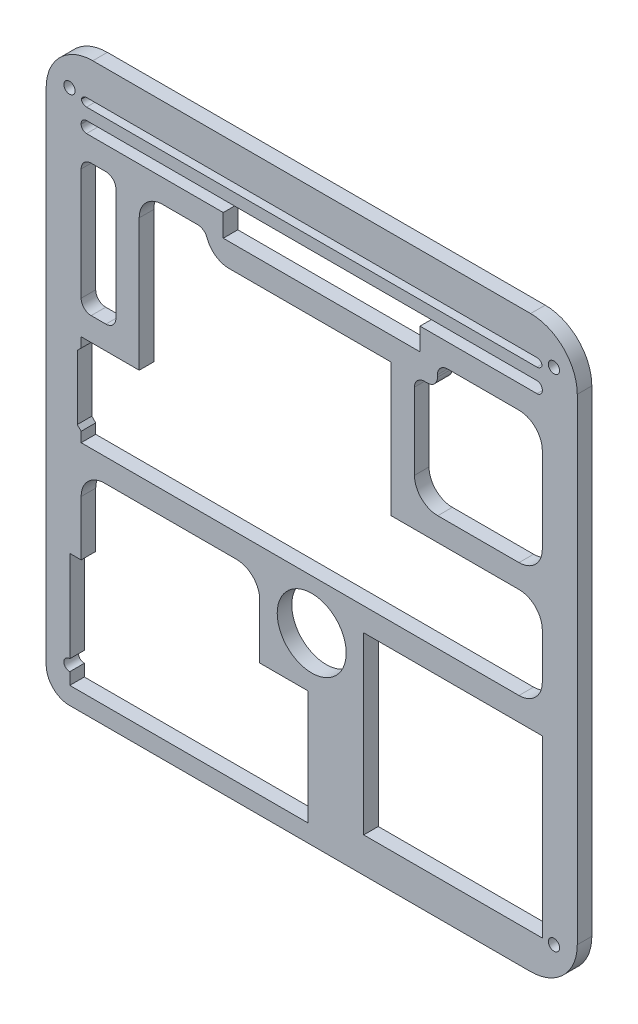
SolidWorks part; units mm, degrees
ref_plane "Front Plane" through (0, 0, 0) normal (0, 0, 1) x (1, 0, 0)
ref_plane "Top Plane" through (0, 0, 0) normal (0, 1, 0) x (1, 0, 0)
ref_plane "Right Plane" through (0, 0, 0) normal (1, 0, 0) x (0, 0, -1)
sketch "Sketch1" plane through (0, 0, 0) normal (0, 0, 1) x (1, 0, 0)
  line L0 (63.9883, 52.5442) -> (63.9883, 48.7342) construction
  line L1 (6.1648, -9.556) -> (64.0322, -9.556)
  line L2 (6.1648, -9.556) -> (6.1648, 52.5442)
  line L3 (6.1648, 52.5442) -> (64.0322, 52.5442)
  line L4 (64.0322, -9.556) -> (64.0322, 52.5442)
  line L5 (60.2222, 48.7342) -> (9.9748, 48.7342)
  line L6 (60.2222, 48.7342) -> (60.2222, -5.746)
  line L7 (60.2222, -5.746) -> (9.9748, -5.746)
  line L8 (9.9748, 48.7342) -> (9.9748, -5.746)
  line L9 (63.9883, 50.6392) -> (18.0707, 50.6392) construction
  line L10 (9.9748, 39.3805) -> (6.1648, 39.3805) construction
  line L11 (8.0698, 39.3805) -> (8.0698, 23.9527) construction
  line L12 (13.5248, -5.746) -> (13.5248, -9.556) construction
  line L13 (13.5248, -7.651) -> (21.1598, -7.651) construction
  line L14 (64.0322, 38.1916) -> (60.2222, 38.1916) construction
  line L15 (62.1272, 38.1916) -> (62.1272, 22.3321) construction
  line L16 (48.6748, 50.6392) -> (23.5288, 50.6392) construction
  line L17 (62.1272, 27.1202) -> (62.1272, 39.363) construction
  line L18 (8.0698, 15.868) -> (8.0698, 3.6252) construction
  line L19 (35.2238, -7.651) -> (34.6952, -7.651) construction
  dimension "D1" = 3.81
  dimension "D2" = 3.81
extrude "Boss-Extrude1" add sketch "Sketch1" along normal blind 1.5875
sketch "Sketch2" plane through (0, 0, 0) normal (0, 0, -1) x (-1, 0, 0)
  line L0 (-60.2222, -5.746) -> (-60.2222, 48.7342) construction
  line L1 (-60.2222, 15.868) -> (-9.9748, 15.868)
  line L2 (-60.2222, 15.868) -> (-60.2222, 13.328)
  line L3 (-60.2222, 13.328) -> (-9.9748, 13.328)
  line L4 (-9.9748, 15.868) -> (-9.9748, 13.328)
  line L5 (-9.9748, 48.7342) -> (-9.9748, -5.746) construction
  line L6 (-13.0532, 15.868) -> (-50.7532, 15.868) construction
  line L8 (-46.8968, 42.9049) -> (-46.8968, 45.3306) construction
  line L9 (-25.4592, 42.9049) -> (-46.8968, 42.9049) construction
  line L10 (-25.4592, 42.9049) -> (-25.4592, 45.3306) construction
  line L11 (-60.2222, 45.3306) -> (-46.8968, 45.3306)
  line L12 (-60.2222, 45.3306) -> (-60.2222, 42.7906)
  line L13 (-60.2222, 42.7906) -> (-48.8018, 42.7906)
  line L14 (-9.9748, 45.3306) -> (-9.9748, 42.7906)
  line L15 (-60.2222, 47.8325) -> (-9.9748, 47.8325)
  line L16 (-60.2222, 47.8325) -> (-60.2222, 46.5625)
  line L17 (-60.2222, 46.5625) -> (-9.9748, 46.5625)
  line L18 (-9.9748, 47.8325) -> (-9.9748, 46.5625)
  line L20 (-55.2788, 45.3306) -> (-16.9248, 45.3306) construction
  line L21 (-55.2788, 46.5625) -> (-16.9248, 46.5625) construction
  line L22 (-46.8968, 42.9049) -> (-46.8968, 45.3306)
  line L23 (-25.4592, 42.9049) -> (-46.8968, 42.9049)
  line L24 (-25.4592, 42.9049) -> (-25.4592, 45.3306)
  line L25 (-48.8018, 42.7906) -> (-48.8018, 40.3649)
  line L26 (-48.8018, 40.3649) -> (-23.5542, 40.3649)
  line L27 (-23.5542, 40.3649) -> (-23.5542, 42.7906)
  line L28 (-23.5542, 42.7906) -> (-9.9748, 42.7906)
  line L29 (-25.4592, 45.3306) -> (-9.9748, 45.3306)
  dimension "D1" = 2.54
  dimension "D2" = 1.905
  dimension "D3" = 2.54
  dimension "D4" = 1.905
  dimension "D5" = 1.27
extrude "Boss-Extrude2" add sketch "Sketch2" against normal up to surface (1.5875 mm away) up to face at (35.0985, 21.4941, 1.5875)
sketch "Sketch3" plane through (0, 0, 0) normal (0, 0, -1) x (-1, 0, 0)
  line L0 (-50.7532, 25.868) -> (-43.7532, 25.868) construction
  line L1 (-50.7532, 25.868) -> (-43.7532, 25.868)
  line L2 (-50.7532, 25.868) -> (-60.2222, 25.868)
  line L3 (-60.2222, 15.868) -> (-60.2222, 42.7906) construction
  line L4 (-60.2222, 25.868) -> (-60.2222, 28.408)
  line L5 (-60.2222, 28.408) -> (-46.2932, 28.408)
  line L6 (-43.7532, 28.408) -> (-43.7532, 25.868)
  line L7 (-43.7532, 28.408) -> (-43.7532, 40.3649)
  line L8 (-48.8018, 40.3649) -> (-23.5542, 40.3649) construction
  line L9 (-43.7532, 40.3649) -> (-46.2932, 40.3649)
  line L10 (-46.2932, 40.3649) -> (-46.2932, 28.408)
  line L11 (-16.3032, 25.868) -> (-13.0532, 25.868) construction
  line L12 (-16.3032, 25.868) -> (-13.0532, 25.868)
  line L13 (-13.0532, 25.868) -> (-9.9748, 25.868)
  line L14 (-9.9748, 42.7906) -> (-9.9748, 15.868) construction
  line L15 (-9.9748, 25.868) -> (-9.9748, 28.408)
  line L16 (-9.9748, 28.408) -> (-13.7632, 28.408)
  line L17 (-13.7632, 28.408) -> (-13.7632, 42.7906)
  line L18 (-23.5542, 42.7906) -> (-9.9748, 42.7906) construction
  line L19 (-13.7632, 42.7906) -> (-16.3032, 42.7906)
  line L20 (-16.3032, 42.7906) -> (-16.3032, 25.868)
  line L21 (-16.3032, 25.868) -> (-16.2412, 25.8471)
  line M22 (-60.2222, 15.868) -> (-60.2222, 42.7906)
  line M25 (-48.8018, 40.3649) -> (-23.5542, 40.3649)
  line M27 (-23.5542, 42.7906) -> (-9.9748, 42.7906)
  line M28 (-9.9748, 42.7906) -> (-9.9748, 15.868)
  dimension "D1" = 2.54
  dimension "D2" = 2.54
  dimension "D3" = 2.54
  dimension "D4" = 2.54
extrude "Boss-Extrude3" add sketch "Sketch3" against normal up to surface (1.5875 mm away) contours L10 L5 L2 L1 L6 L7 M25 M22 | L20 L12 L13 L16 L17 M27 M28 region at (55.4877, 26.0875, 0) region at (14.4544, 33.0139, 0) up to face at (35.0985, 48.2834, 1.5875)
sketch "Sketch4" plane through (0, 0, 0) normal (0, 0, -1) x (-1, 0, 0)
  line L0 (-60.2222, 13.328) -> (-9.9748, 13.328) construction
  line L1 (-40.7627, 13.328) -> (-29.4343, 13.328)
  line L2 (-40.7627, 13.328) -> (-40.7627, -5.746)
  line L3 (-40.7627, -5.746) -> (-29.4343, -5.746)
  line L4 (-29.4343, 13.328) -> (-29.4343, -5.746)
  line L5 (-9.9748, -5.746) -> (-60.2222, -5.746) construction
  line L6 (-38.8577, 10.4578) -> (-40.7627, 10.4578) construction
  line L7 (-31.3393, 10.4578) -> (-29.4343, 10.4578) construction
  circle A0 centre (-35.0985, 10.4578) radius 3.7592 construction
  dimension "D1" = 1.905
extrude "Boss-Extrude4" add sketch "Sketch4" against normal up to surface (1.5875 mm away) up to face at (11.869, 35.5993, 1.5875)
sketch "Sketch5" plane through (0, 0, 0) normal (0, 0, -1) x (-1, 0, 0)
  line L0 (-8.7364, 4.8077) -> (-34.6952, 4.8077) construction
  line L3 (-34.6952, -7.651) -> (-34.6952, 4.8077) construction
  line L4 (-8.7364, -7.651) -> (-34.6952, -7.651) construction
  line L5 (-8.7364, -7.651) -> (-8.7364, 4.8077) construction
  line L6 (-8.7364, 4.8077) -> (-34.6952, 4.8077)
  line L7 (-34.6952, -7.651) -> (-34.6952, 4.8077)
  line L8 (-8.7364, -7.651) -> (-34.6952, -7.651)
  line L9 (-8.7364, -7.651) -> (-8.7364, 4.8077)
  circle A0 centre (-35.0985, 10.4578) radius 3.7592 construction
  circle A1 centre (-35.0985, 10.4578) radius 3.7592
extrude "Cut-Extrude1" cut sketch "Sketch5" against normal up to surface (1.5875 mm away) up to face at (50.4924, 3.791, 1.5875)
fillet "Fillet1" radius 5.08 3 edges at (64.0322, -9.556, 0.7937) (6.1648, 52.5442, 0.7937) (64.0322, 52.5442, 0.7937)
fillet "Fillet2" radius 2.54 9 edges at (16.3032, 42.7906, 0.7937) (23.5542, 40.3649, 0.7937) (60.2222, 42.7906, 0.7937) (46.2932, 28.408, 0.7937) (60.2222, 15.868, 0.7937) (60.2222, 28.408, 0.7937) (9.9748, 13.328, 0.7937) (29.4343, 13.328, 0.7937) (60.2222, 25.868, 0.7937)
fillet "Fillet3" radius 1.0922 8 edges at (46.2932, 40.3649, 0.7937) (48.8018, 40.3649, 0.7937) (48.8018, 42.7906, 0.7937) (9.9748, 28.408, 0.7937) (13.7632, 28.408, 0.7937) (9.9748, 42.7906, 0.7937) (13.7632, 42.7906, 0.7937) (23.5542, 42.7906, 0.7937)
fillet "Fillet4" radius 0.5842 8 edges at (9.9748, 45.3306, 0.7937) (9.9748, 47.8325, 0.7937) (9.9748, 48.7342, 0.7937) (9.9748, 46.5625, 0.7937) (60.2222, 47.8325, 0.7937) (60.2222, 48.7342, 0.7937) (60.2222, 46.5625, 0.7937) (60.2222, 45.3306, 0.7937)
fillet "Fillet5" radius 2.54 1 edges at (6.1648, -9.556, 0.7937)
sketch "Sketch6" plane through (0, 0, 0) normal (0, 0, -1) x (-1, 0, 0)
  line L0 (-9.5532, 17.368) -> (-11.0532, 15.868) construction
  line L1 (-11.0532, 25.868) -> (-9.5532, 24.368) construction
  line L2 (-9.5532, 24.368) -> (-9.5532, 17.368) construction
  line L3 (-9.5532, 17.368) -> (-11.0532, 15.868)
  line L4 (-11.0532, 25.868) -> (-9.5532, 24.368)
  line L5 (-9.5532, 24.368) -> (-9.5532, 17.368)
  line L6 (-11.0532, 25.868) -> (-11.0532, 15.868)
  circle A0 centre (-61.4922, 48.7342) radius 0.6096 construction
  circle A1 centre (-8.7048, 48.7342) radius 0.6096 construction
  circle A2 centre (-61.4922, -5.746) radius 0.6096 construction
  circle A3 centre (-8.7048, -5.746) radius 0.6096 construction
  circle A4 centre (-61.4922, 48.7342) radius 0.6096
  circle A5 centre (-8.7048, 48.7342) radius 0.6096
  circle A6 centre (-61.4922, -5.746) radius 0.6096
  circle A7 centre (-8.7048, -5.746) radius 0.6096
extrude "Cut-Extrude2" cut sketch "Sketch6" against normal up to surface (1.5875 mm away) up to face at (31.3393, 10.4578, 1.5875)
